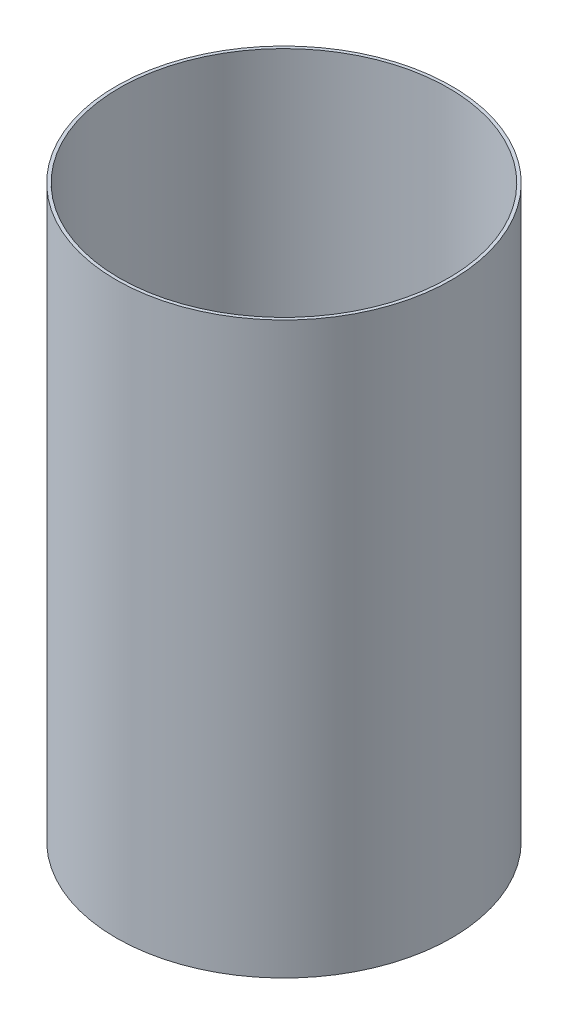
SolidWorks part; units mm, degrees
material "Hexcel AS4C (3000 Filaments)"
ref_plane "Front" through (0, 0, 0) normal (0, 0, 1) x (1, 0, 0)
ref_plane "Top" through (0, 0, 0) normal (0, 1, 0) x (1, 0, 0)
ref_plane "Right" through (0, 0, 0) normal (1, 0, 0) x (0, 0, -1)
sketch "Sketch1" plane through (0, 0, 0) normal (0, 1, 0) x (1, 0, 0)
  circle A0 centre (0, 0) radius 67.31
  circle A1 centre (0, 0) radius 66.04
  dimension "D1" = 134.62
  dimension "D2" = 132.08
extrude "Boss-Extrude1" add sketch "Sketch1" along normal mid plane 228.6
ref_axis "Axis1" through (0, 114.3, 0) along (0, -1, 0)
